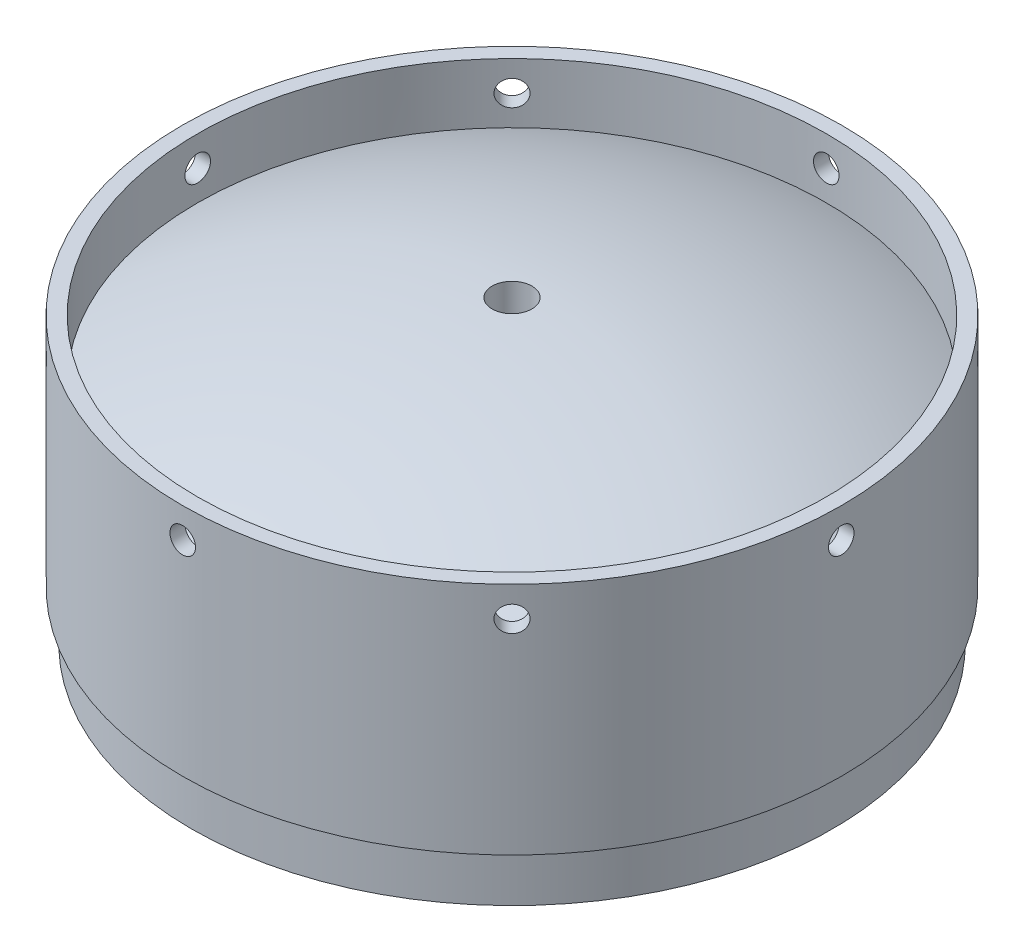
SolidWorks part; units mm, degrees
material "6061-T6 (SS)"
ref_plane "Front Plane" through (0, 0, 0) normal (0, 0, 1) x (1, 0, 0)
ref_plane "Top Plane" through (0, 0, 0) normal (0, 1, 0) x (1, 0, 0)
ref_plane "Right Plane" through (0, 0, 0) normal (1, 0, 0) x (0, 0, -1)
ref_axis "Axis1" through (0, 127.061, 0) along (0, -1, 0)
sketch "Sketch1" plane through (0, 0, 0) normal (0, 0, 1) x (1, 0, 0)
  line L0 (-69.85, 10.6249) -> (-69.85, 60.325)
  line L1 (-67.945, 9.525) -> (-69.85, 10.6249)
  line L2 (0, 127.061) -> (0, -81.9141) construction
  line L4 (-67.945, 9.525) -> (-67.945, 0)
  line L5 (-67.945, 0) -> (-66.675, 0)
  line L6 (55, 0) -> (-55, 0) construction
  line L7 (-66.675, 60.325) -> (-69.85, 60.325)
  line L8 (-69.85, 10.6249) -> (-67.945, 9.525)
  line L10 (-4.2164, 63.5936) -> (-4.2164, 56.6056)
  line L11 (-66.675, 47.625) -> (-66.675, 60.325)
  line L15 (-66.675, 0) -> (-66.675, 9.525)
  line L16 (-66.675, 9.525) -> (-63.1965, 29.2524)
  arc A0 (-63.1965, 29.2524) -> (-51.117, 46.9813) centre (-44.1465, 29.2524) cw
  arc A1 (-51.117, 46.9813) -> (-4.2164, 56.6056) centre (0, -83.0308) cw
  arc A3 (-66.675, 47.625) -> (-4.2164, 63.5936) centre (0, -83.0308) cw
  point P14 (-67.31, 0)
  dimension "D5" = 19.05
  dimension "D6" = 139.7
  dimension "D7" = 146.685
  dimension "D8" = 50.8
  dimension "D2" = 170
  dimension "D3" = 9.525
  dimension "D4" = 1.27
  dimension "D9" = 12.7
  dimension "D10" = 3.175
  dimension "D13" = 4.2164
  dimension "D15" = 3.175
  dimension "D16" = 69.85
  dimension "D17" = 120
revolve "Revolve2" add sketch "Sketch1" angle 360 about axis through (0, 127.061, 0) along (0, -1, 0) region at (-68.9361, 35.4749, 0)
sketch "Sketch2" plane through (0, 0, 0) normal (0, 0, 1) x (1, 0, 0)
  line L0 (0, 127.061) -> (0, -81.9141) construction
  line L1 (0, 87.1374) -> (-97.8719, 87.1374)
  line L2 (0, 87.1374) -> (0, -26.2798)
  line L3 (0, -26.2798) -> (-97.8719, -26.2798)
  line L4 (-97.8719, 87.1374) -> (-97.8719, -26.2798)
revolve "Cut-Revolve1" [suppressed] cut sketch "Sketch2" angle 315 about axis through (0, 127.061, 0) along (0, -1, 0)
ref_plane "Plane1" through (0, 53.975, 0) normal (0, 1, 0) x (1, 0, 0)
ref_axis "Axis2" through (0, 53.975, -88.99) along (0, 0, 1)
hole_wizard "#3 (0.213) Diameter Hole1" positions "3DSketch3" profile "Sketch5" hole size "#3" standard "ANSI Inch" end condition up to next
sketch3d "3DSketch3"
  line L0 (0, 53.975, -88.99) -> (0, 53.975, 88.99) construction
  point P0 (0, 53.975, 69.85)
sketch "Sketch5" plane through (0, 53.975, 69.85) normal (1, 0, 0) x (0, -1, 0)
  line L0 (0, 0) -> (0, 3.175)
  line L1 (0, 3.175) -> (2.7051, 3.175)
  line L2 (2.7051, 3.175) -> (2.7051, 0)
  line L5 (2.7051, 0) -> (0, 0)
  line L11 (0, -6.35) -> (0, 107.95) construction
  dimension "Thru Hole Dia." = 5.4102
  dimension "Thru Hole Depth" = 3.175
pattern_circular "CirPattern1" count 8 over 360 about axis through (0, 127.061, 0) along (0, -1, 0) of "#3 (0.213) Diameter Hole1"
cosmetic thread "Cosmetic Thread1" parameters "D2"=6.35
ref_plane "Plane2" through (0, 9.525, 0) normal (0, -1, 0) x (-1, 0, 0)
sketch "Sketch7" plane through (0, 9.525, 0) normal (0, -1, 0) x (-1, 0, 0)
  circle A0 centre (0, 0) radius 56.515
  dimension "D1" = 113.03
extrude "Boss-Extrude2" [suppressed] add sketch "Sketch7" against normal blind 41.91 separate body
combine bodies "Combine2" [suppressed] operation type subtract main body 113 bodies to subtract 110
sketch "Sketch8" plane through (0, 0, 0) normal (0, 0, 1) x (1, 0, 0)
  line L0 (0, 127.061) -> (0, -81.9141) construction
  line L1 (0, 89.8009) -> (92.4947, 89.8009)
  line L2 (0, 89.8009) -> (0, -18.1338)
  line L3 (0, -18.1338) -> (92.4947, -18.1338)
  line L4 (92.4947, 89.8009) -> (92.4947, -18.1338)
revolve "Cut-Revolve2" [suppressed] cut sketch "Sketch8" angle 300 about axis through (0, 127.061, 0) along (0, -1, 0) other way angle 30 reverse direction yes
